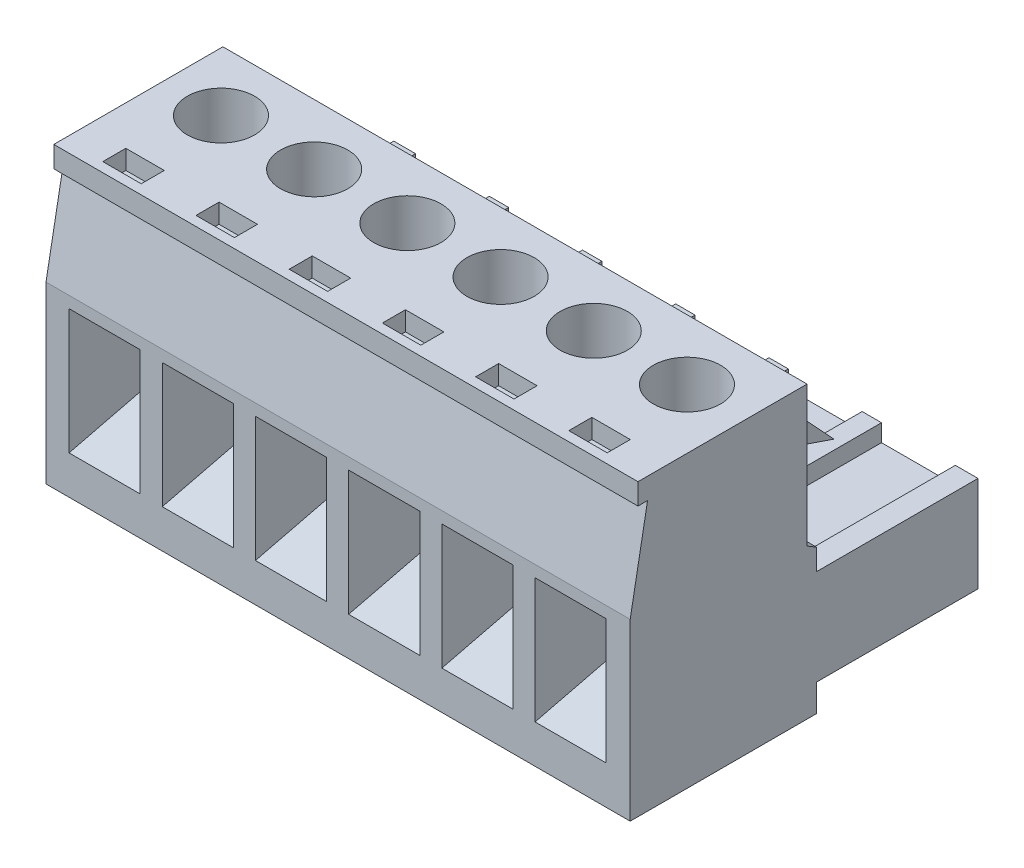
SolidWorks part; units mm, degrees
ref_plane "Front Plane" through (0, 0, 0) normal (0, 0, 1) x (1, 0, 0)
ref_plane "Top Plane" through (0, 0, 0) normal (0, 1, 0) x (1, 0, 0)
ref_plane "Right Plane" through (0, 0, 0) normal (1, 0, 0) x (0, 0, -1)
sketch "Sketch1" plane through (0, 0, 0) normal (1, 0, 0) x (0, 0, -1)
  line L0 (0, 0) -> (0, -1.1)
  line L1 (0, -1.1) -> (0.5, -1.1)
  line L2 (0.5, -1.1) -> (-0.405, -6)
  line L3 (-0.405, -6) -> (-0.405, -15.1)
  line L4 (-0.405, -15.1) -> (9.295, -15.1)
  line L10 (9.295, -7.6) -> (8.8, -7.3)
  line L11 (8.8, -7.3) -> (8.8, 0)
  line L12 (8.8, 0) -> (0, 0)
  line L14 (9.295, -7.6) -> (9.295, -15.1)
  point P4 (8.8, -6.7897)
  dimension "D1" = 8.8
  dimension "D2" = 15.1
  dimension "D3" = 1.1
  dimension "D4" = 9.1
  dimension "D5" = 8.3
  dimension "D6" = 7.5
  dimension "D7" = 7.3
  dimension "D10" = 9.7
extrude "Boss-Extrude1" add sketch "Sketch1" along normal mid plane 30.4
sketch "Sketch6" plane through (0, 0, -9.295) normal (0, 0, -1) x (-1, 0, 0)
  line L0 (-15.2, -15.1) -> (-15.2, -7.6) construction
  line L1 (-15.2, -8.7) -> (-14.0205, -8.7)
  line L2 (-15.2, -8.7) -> (-15.2, -13.6797)
  line L3 (-15.2, -13.6797) -> (-13.8219, -13.6797)
  line L4 (15.2, -8.7) -> (15.2, -13.6797)
  line L5 (15.2, -15.1) -> (15.2, -7.6) construction
  line L6 (-10.3781, -13.6797) -> (-8.9719, -13.6797)
  line L7 (-13.8191, -14.3) -> (-2.5994, -14.3) construction
  line L8 (-15.2, 0) -> (15.2, 0) construction
  line L9 (-14.2, -6.3903) -> (-14.2, -15.3783) construction
  line L10 (-10.1795, -8.7) -> (-9.1705, -8.7)
  line L12 (-14.0205, -8.7) -> (-14.0205, -9.6)
  line L13 (-14.0205, -9.6) -> (-10.1795, -9.6)
  line L14 (-10.1795, -8.7) -> (-10.1795, -9.6)
  line L15 (-9.1705, -8.7) -> (-9.1705, -9.6)
  line L16 (-9.1705, -9.6) -> (-5.3295, -9.6)
  line L17 (-5.3295, -8.7) -> (-5.3295, -9.6)
  line L18 (-4.3205, -8.7) -> (-4.3205, -9.6)
  line L19 (-4.3205, -9.6) -> (-0.4795, -9.6)
  line L20 (-0.4795, -8.7) -> (-0.4795, -9.6)
  line L21 (0.5295, -8.7) -> (0.5295, -9.6)
  line L22 (0.5295, -9.6) -> (4.3705, -9.6)
  line L23 (4.3705, -8.7) -> (4.3705, -9.6)
  line L24 (5.3795, -8.7) -> (5.3795, -9.6)
  line L25 (5.3795, -9.6) -> (9.2205, -9.6)
  line L26 (9.2205, -8.7) -> (9.2205, -9.6)
  line L27 (10.2295, -8.7) -> (10.2295, -9.6)
  line L28 (10.2295, -9.6) -> (14.0705, -9.6)
  line L29 (14.0705, -8.7) -> (14.0705, -9.6)
  line L30 (-5.3295, -8.7) -> (-4.3205, -8.7)
  line L31 (-0.4795, -8.7) -> (0.5295, -8.7)
  line L32 (4.3705, -8.7) -> (5.3795, -8.7)
  line L33 (9.2205, -8.7) -> (10.2295, -8.7)
  line L34 (14.0705, -8.7) -> (15.2, -8.7)
  line L35 (-5.5281, -13.6797) -> (-4.1219, -13.6797)
  line L36 (-0.6781, -13.6797) -> (0.7281, -13.6797)
  line L37 (4.1719, -13.6797) -> (5.5781, -13.6797)
  line L38 (9.0219, -13.6797) -> (10.4281, -13.6797)
  line L39 (13.8719, -13.6797) -> (15.2, -13.6797)
  circle A0 centre (-12.1, -11.6) radius 2.1 construction
  arc A1 (-13.8219, -13.6797) -> (-10.3781, -13.6797) centre (-12.1, -11.6) ccw
  circle A2 centre (-12.1, -11.6) radius 1.4 construction
  arc A3 (-8.9719, -13.6797) -> (-5.5281, -13.6797) centre (-7.25, -11.6) ccw
  arc A4 (-4.1219, -13.6797) -> (-0.6781, -13.6797) centre (-2.4, -11.6) ccw
  arc A5 (0.7281, -13.6797) -> (4.1719, -13.6797) centre (2.45, -11.6) ccw
  arc A6 (5.5781, -13.6797) -> (9.0219, -13.6797) centre (7.3, -11.6) ccw
  arc A7 (10.4281, -13.6797) -> (13.8719, -13.6797) centre (12.15, -11.6) ccw
  point P23 (-12.1, -9.6)
  dimension "D1" = 4.2
  dimension "D2" = 1.3
  dimension "D6" = 0.7
  dimension "D3" = 5.6
  dimension "D4" = 8.7
  dimension "D5" = 1
  dimension "D7" = 4.7
  dimension "D8" = 6
extrude "Boss-Extrude2" add sketch "Sketch6" along normal blind 8.4
sketch "Sketch10" plane through (0, 0, -17.695) normal (0, 0, -1) x (-1, 0, 0)
  point P0 (-12.1, -11.6)
hole_wizard "CBORE for M5 Hex Head Bolt1" positions "Sketch10" profile "Sketch11" counterbore size "M5" standard "ANSI Metric"
sketch "Sketch11" plane through (12.1, -11.6, -17.695) normal (1, 0, 0) x (0, 1, 0)
  line L0 (0, 0) -> (0, 8.7004)
  line L1 (0, 8.7004) -> (0.5, 8.4)
  line L2 (0.5, 8.4) -> (0.5, 3)
  line L3 (0.5, 3) -> (1.5, 3)
  line L4 (1.5, 3) -> (1.5, 0)
  line L5 (1.5, 0) -> (0, 0)
  line L10 (0, 8.7004) -> (-0.5, 8.4) construction
  line L11 (0, -6.35) -> (0, 107.95) construction
  dimension "Hole Dia." = 1
  dimension "Hole Depth" = 8.4
  dimension "C'Bore Dia." = 3
  dimension "C'Bore Depth" = 3
  dimension "Drill Angle" = 118
pattern_linear "LPattern1" count 6 spacing 4.85 along (-1, 0, 0) of "CBORE for M5 Hex Head Bolt1"
sketch "Sketch12" plane through (0, 0, -17.695) normal (0, 0, -1) x (-1, 0, 0)
  line L0 (-10.6303, -13.1) -> (-8.7197, -13.1)
  line L1 (-9.675, -9.9732) -> (-9.675, -13.1) construction
  line L4 (-10.3561, -10.4301) -> (-9.675, -9.9732)
  line L5 (-8.9939, -10.4301) -> (-9.675, -9.9732)
  circle A0 centre (-12.1, -11.6) radius 2.1 construction
  arc A1 (-10.6303, -13.1) -> (-10.3561, -10.4301) centre (-12.1, -11.6) ccw
  arc A2 (-8.7197, -13.1) -> (-8.9939, -10.4301) centre (-7.25, -11.6) cw
  circle A3 centre (-12.1, -11.6) radius 1.5 construction
extrude "Cut-Extrude1" cut sketch "Sketch12" against normal blind 3
pattern_linear "LPattern2" count 5 spacing 4.85 along (-1, 0, 0) of "Cut-Extrude1"
sketch "Sketch13" plane through (0, 0, 0.405) normal (0, 0, 1) x (1, 0, 0)
  line L0 (-15.2, -6) -> (-15.2, -15.1) construction
  line L1 (-14, -6.6) -> (-10.3, -6.6)
  line L2 (-14, -6.6) -> (-14, -13.1)
  line L3 (-14, -13.1) -> (-10.3, -13.1)
  line L4 (-10.3, -6.6) -> (-10.3, -13.1)
  line L5 (15.2, 0) -> (-15.2, 0) construction
  line L6 (15.2, -15.1) -> (-15.2, -15.1) construction
  dimension "D1" = 1.2
  dimension "D2" = 3.7
  dimension "D3" = 6.6
  dimension "D4" = 2
ref_plane "Plane1" through (0, 0, -3.495) normal (0, 0, 1) x (1, 0, 0)
sketch "Sketch14" plane through (0, 0, -3.495) normal (0, 0, 1) x (1, 0, 0)
  line L1 (-13.8, -8.8) -> (-10.5, -8.8)
  line L2 (-13.8, -8.8) -> (-13.8, -11.9)
  line L3 (-13.8, -11.9) -> (-10.5, -11.9)
  line L4 (-10.5, -8.8) -> (-10.5, -11.9)
  line L5 (15.2, 0) -> (-15.2, 0) construction
  line L6 (15.2, -15.1) -> (-15.2, -15.1) construction
  line L7 (-14, -6.6) -> (-14, -13.1) construction
  line L8 (-10.3, -6.6) -> (-10.3, -13.1) construction
  dimension "D1" = 8.8
  dimension "D2" = 3.2
  dimension "D3" = 0.2
  dimension "D4" = 0.2
loft "Cut-Loft1" cut profiles "Sketch14", "Sketch13" connector at (-13.8, -8.8, -3.495) connector at (-14, -6.6, 0.405)
extrude "Cut-Extrude2" cut sketch "Sketch14<3>" against normal blind 3
sketch "Sketch14<3>" plane through (0, 0, -3.495) normal (0, 0, 1) x (1, 0, 0) same geometry as "Sketch14"
pattern_linear "LPattern3" count 6 spacing 4.85 along (1, 0, 0) of "Cut-Loft1", "Cut-Extrude2"
sketch "Sketch15" plane through (15.2, 0, 0) normal (1, 0, 0) x (0, 0, -1)
  line L0 (8.8, -6.2) -> (12.2921, -6.2)
  line L1 (8.8, -7.3) -> (8.8, 0) construction
  line L2 (12.2921, -6.2) -> (13.695, -6.6816)
  line L3 (13.695, -6.6816) -> (12.1336, -4.9928)
  line L4 (12.1336, -4.9928) -> (8.8, -4.8)
  line L5 (8.8, -4.8) -> (8.8, -6.2)
  line L6 (-0.405, -6) -> (-0.405, -15.1) construction
  point P4 (0, 0)
  point P10 (13.1435, -5.2867)
  point P11 (12.9363, -4.6473)
  point P12 (12.1619, -5.8721)
  point P13 (12.9363, -6.4394)
  point P14 (12.6121, -6.2323)
  point P15 (12.5436, -5.0165)
  point P16 (8.8, -4.5936)
  point P18 (12.2921, -6.2)
  point P19 (13.695, -6.6816)
  dimension "D1" = 14.1
  dimension "D2" = 2.3
  dimension "D3" = 4.8
  dimension "D4" = 1.4
extrude "Boss-Extrude3" add sketch "Sketch15" along normal blind 1.5 from offset 5 offset against normal yes
mirror "Mirror1" about plane through (0, 0, 0) normal (1, 0, 0) of "Boss-Extrude3"
sketch "Sketch16" plane through (0, 0, 0) normal (0, 1, 0) x (1, 0, 0)
  line L0 (-15.2, 8.8) -> (-15.2, 0) construction
  line L1 (15.2, 8.8) -> (-15.2, 8.8) construction
  point P0 (-12.15, 5.65)
  dimension "D1" = 3.05
  dimension "D2" = 3.15
hole_wizard "CBORE for M5 Hex Head Bolt2" positions "Sketch16" profile "Sketch17" counterbore size "M5" standard "ANSI Metric"
sketch "Sketch17" plane through (-12.15, 0, -5.65) normal (1, 0, 0) x (0, 0, 1)
  line L0 (0, 0) -> (0, 8.8)
  line L1 (0, 8.8) -> (1, 8.8)
  line L2 (1, 8.8) -> (1, 3)
  line L3 (1, 3) -> (1.75, 3)
  line L4 (1.75, 3) -> (1.75, 0)
  line L5 (1.75, 0) -> (0, 0)
  line L10 (0, 8.8) -> (-1, 8.8) construction
  line L11 (0, -6.35) -> (0, 107.95) construction
  dimension "Hole Dia." = 2
  dimension "Hole Depth" = 8.8
  dimension "C'Bore Dia." = 3.5
  dimension "C'Bore Depth" = 3
  dimension "Drill Angle" = 180
pattern_linear "LPattern4" count 6 spacing 4.85 along (1, 0, 0) of "CBORE for M5 Hex Head Bolt2"
sketch "Sketch19" plane through (0, 0, 0) normal (0, 1, 0) x (1, 0, 0)
  line L1 (-14.7, 8.8) -> (14.7, 8.8)
  line L2 (-14.7, 8.8) -> (-14.7, 6.3)
  line L3 (-14.7, 6.3) -> (-14.3041, 6.3)
  line L4 (14.7, 8.8) -> (14.7, 6.3)
  line L5 (-9.9959, 6.3) -> (-9.4541, 6.3)
  line L6 (-5.1459, 6.3) -> (-4.6041, 6.3)
  line L7 (-0.2959, 6.3) -> (0.2459, 6.3)
  line L8 (4.5541, 6.3) -> (5.0959, 6.3)
  line L9 (9.4041, 6.3) -> (9.9459, 6.3)
  line L10 (14.2541, 6.3) -> (14.7, 6.3)
  line L11 (-15.2, 8.8) -> (-15.2, 0) construction
  line L12 (15.2, 8.8) -> (15.2, 0) construction
  circle A3 centre (-12.15, 5.65) radius 2.25
  arc A4 (-9.9959, 6.3) -> (-14.3041, 6.3) centre (-12.15, 5.65) ccw
  circle A6 centre (-7.3, 5.65) radius 2.25
  arc A7 (-5.1459, 6.3) -> (-9.4541, 6.3) centre (-7.3, 5.65) ccw
  circle A9 centre (-2.45, 5.65) radius 2.25
  arc A10 (-0.2959, 6.3) -> (-4.6041, 6.3) centre (-2.45, 5.65) ccw
  circle A12 centre (2.4, 5.65) radius 2.25
  arc A13 (4.5541, 6.3) -> (0.2459, 6.3) centre (2.4, 5.65) ccw
  circle A15 centre (7.25, 5.65) radius 2.25
  arc A16 (9.4041, 6.3) -> (5.0959, 6.3) centre (7.25, 5.65) ccw
  circle A18 centre (12.1, 5.65) radius 2.25
  arc A19 (14.2541, 6.3) -> (9.9459, 6.3) centre (12.1, 5.65) ccw
  dimension "D7" = 2.5
  dimension "D8" = 0.5
  dimension "D9" = 0.5
  dimension "D1" = 0.5
  dimension "D2" = 0.5
  dimension "D3" = 0.5
  dimension "D4" = 0.5
  dimension "D5" = 0.5
  dimension "D6" = 0.5
extrude "Cut-Extrude4" cut sketch "Sketch19" against normal blind 1.5 from offset 1.3 offset against normal yes
sketch "Sketch20" plane through (0, 0, 0) normal (0, 1, 0) x (1, 0, 0)
  line L0 (-15.2, 8.8) -> (-15.2, 0) construction
  line L1 (-13.15, 1.7) -> (-11.15, 1.7)
  line L2 (-13.15, 1.7) -> (-13.15, 0.5)
  line L3 (-13.15, 0.5) -> (-11.15, 0.5)
  line L4 (-11.15, 1.7) -> (-11.15, 0.5)
  line L5 (-13.15, 1.7) -> (-11.15, 0.5) construction
  line L6 (-13.15, 0.5) -> (-11.15, 1.7) construction
  line L7 (15.2, 0) -> (-15.2, 0) construction
  line L8 (-8.3, 1.7) -> (-6.3, 1.7)
  line L9 (-8.3, 1.7) -> (-8.3, 0.5)
  line L10 (-8.3, 0.5) -> (-6.3, 0.5)
  line L11 (-6.3, 1.7) -> (-6.3, 0.5)
  line L12 (-8.3, 1.7) -> (-6.3, 0.5) construction
  line L13 (-8.3, 0.5) -> (-6.3, 1.7) construction
  line L14 (-3.45, 1.7) -> (-1.45, 1.7)
  line L15 (-3.45, 1.7) -> (-3.45, 0.5)
  line L16 (-3.45, 0.5) -> (-1.45, 0.5)
  line L17 (-1.45, 1.7) -> (-1.45, 0.5)
  line L18 (-3.45, 1.7) -> (-1.45, 0.5) construction
  line L19 (-3.45, 0.5) -> (-1.45, 1.7) construction
  line L20 (1.4, 1.7) -> (3.4, 1.7)
  line L21 (1.4, 1.7) -> (1.4, 0.5)
  line L22 (1.4, 0.5) -> (3.4, 0.5)
  line L23 (3.4, 1.7) -> (3.4, 0.5)
  line L24 (1.4, 1.7) -> (3.4, 0.5) construction
  line L25 (1.4, 0.5) -> (3.4, 1.7) construction
  line L26 (6.25, 1.7) -> (8.25, 1.7)
  line L27 (6.25, 1.7) -> (6.25, 0.5)
  line L28 (6.25, 0.5) -> (8.25, 0.5)
  line L29 (8.25, 1.7) -> (8.25, 0.5)
  line L30 (6.25, 1.7) -> (8.25, 0.5) construction
  line L31 (6.25, 0.5) -> (8.25, 1.7) construction
  line L32 (11.1, 1.7) -> (13.1, 1.7)
  line L33 (11.1, 1.7) -> (11.1, 0.5)
  line L34 (11.1, 0.5) -> (13.1, 0.5)
  line L35 (13.1, 1.7) -> (13.1, 0.5)
  line L36 (11.1, 1.7) -> (13.1, 0.5) construction
  line L37 (11.1, 0.5) -> (13.1, 1.7) construction
  point P0 (-12.15, 1.1)
  point P11 (-7.3, 1.1)
  point P16 (-2.45, 1.1)
  point P21 (2.4, 1.1)
  point P26 (7.25, 1.1)
  point P31 (12.1, 1.1)
  dimension "D1" = 3.05
  dimension "D2" = 2
  dimension "D3" = 1.2
  dimension "D4" = 0.5
  dimension "D5" = 6
extrude "Cut-Extrude5" cut sketch "Sketch20" against normal blind 1
